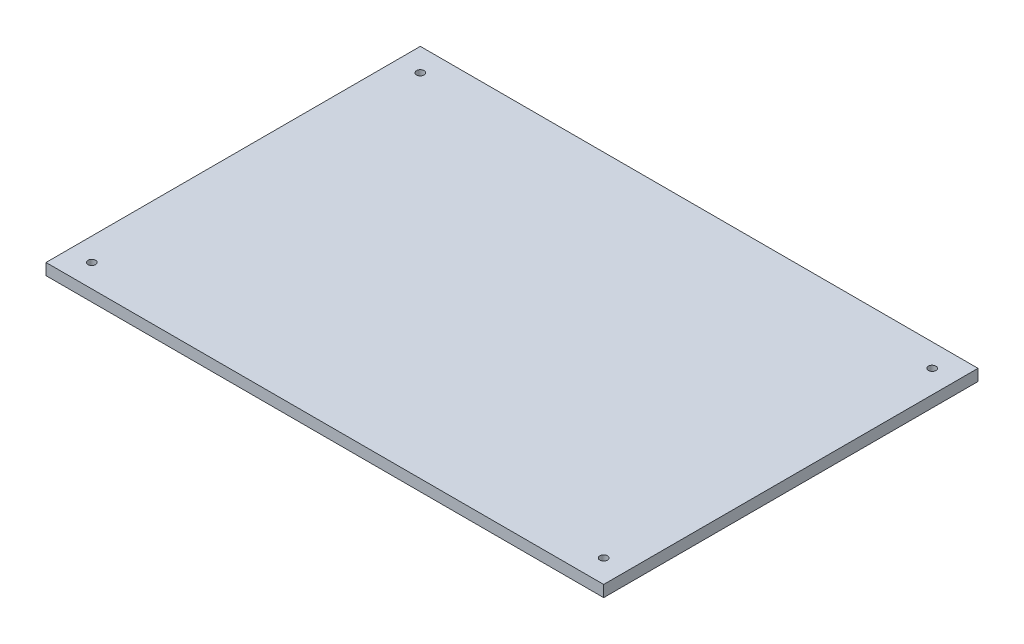
SolidWorks part; units mm, degrees
ref_plane "Front Plane" through (0, 0, 0) normal (0, 0, 1) x (1, 0, 0)
ref_plane "Top Plane" through (0, 0, 0) normal (0, 1, 0) x (1, 0, 0)
ref_plane "Right Plane" through (0, 0, 0) normal (1, 0, 0) x (0, 0, -1)
sketch "Sketch1" plane through (0, 0, 0) normal (0, 1, 0) x (1, 0, 0)
  line L1 (0, 0) -> (463.55, 0)
  line L2 (0, 0) -> (0, -311.15)
  line L3 (0, -311.15) -> (463.55, -311.15)
  line L4 (463.55, 0) -> (463.55, -311.15)
  dimension "D1" = 463.55
  dimension "D2" = 311.15
extrude "Boss-Extrude1" add sketch "Sketch1" along normal blind 9.525
sketch "Sketch2" plane through (0, 9.525, 0) normal (0, 1, 0) x (1, 0, 0)
  line L0 (463.55, 0) -> (0, 0) construction
  line L1 (463.55, -311.15) -> (463.55, 0) construction
  line L2 (231.775, 0) -> (231.775, -311.15) construction
  line L3 (0, -311.15) -> (463.55, -311.15) construction
  line L4 (0, -155.575) -> (463.55, -155.575) construction
  line L5 (0, 0) -> (0, -311.15) construction
  circle A0 centre (444.5, -19.05) radius 3.175
  circle A1 centre (19.05, -19.05) radius 3.175
  circle A2 centre (444.5, -292.1) radius 3.175
  circle A3 centre (19.05, -292.1) radius 3.175
  dimension "D1" = 6.35
  dimension "D2" = 273.05
  dimension "D3" = 425.45
extrude "Cut-Extrude1" cut sketch "Sketch2" against normal up to surface (9.525 mm away) up to face at (231.775, 0, 155.575)
sketch "Sketch4" plane through (0, 9.525, 0) normal (0, 1, 0) x (1, 0, 0)
  line L0 (38.1, 0) -> (38.1, -311.15) construction
  line L1 (463.55, 0) -> (0, 0) construction
  line L2 (0, -311.15) -> (463.55, -311.15) construction
  line L3 (425.45, 0) -> (425.45, -311.15) construction
  line L4 (0, -38.1) -> (463.55, -38.1) construction
  line L5 (0, 0) -> (0, -311.15) construction
  line L6 (463.55, -311.15) -> (463.55, 0) construction
  line L7 (0, -273.05) -> (463.55, -273.05) construction
  point P16 (38.1, -155.575)
  point P17 (425.45, -155.575)
  dimension "D1" = 38.1
  dimension "D2" = 38.1
  dimension "D3" = 38.1
  dimension "D4" = 38.1
